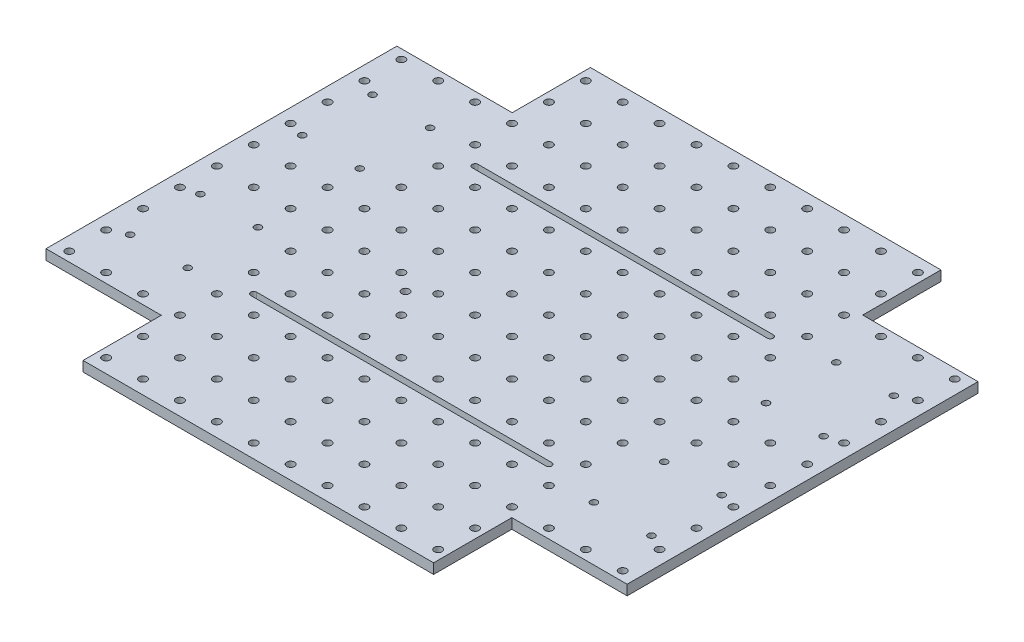
SolidWorks part; units mm, degrees
ref_plane "Front Plane" through (0, 0, 0) normal (0, 0, 1) x (1, 0, 0)
ref_plane "Top Plane" through (0, 0, 0) normal (0, 1, 0) x (1, 0, 0)
ref_plane "Right Plane" through (0, 0, 0) normal (1, 0, 0) x (0, 0, -1)
sketch "Sketch1" plane through (0, 0, 0) normal (0, 1, 0) x (1, 0, 0)
  line L0 (95, -95.1) -> (157.5, -95.1)
  line L1 (-157.5, 95.1) -> (-95, 95.1)
  line L2 (-157.5, 95.1) -> (-157.5, -95.1)
  line L3 (-157.5, -95.1) -> (-95, -95.1)
  line L4 (157.5, 95.1) -> (157.5, -95.1)
  line L5 (-157.5, 95.1) -> (157.5, -95.1) construction
  line L6 (-157.5, -95.1) -> (157.5, 95.1) construction
  line L7 (95, 137.5) -> (-95, 137.5)
  line L8 (95, 137.5) -> (95, 95.1)
  line L9 (95, -137.5) -> (-95, -137.5)
  line L10 (-95, 137.5) -> (-95, 95.1)
  line L11 (95, 137.5) -> (-95, -137.5) construction
  line L12 (95, -137.5) -> (-95, 137.5) construction
  line L13 (95, -95.1) -> (95, -137.5)
  line L14 (-95, -95.1) -> (-95, -137.5)
  line L15 (95, 95.1) -> (157.5, 95.1)
  point P0 (0, 0)
  point P6 (0, 0)
  dimension "D1" = 315
  dimension "D2" = 42.4
  dimension "D3" = 275
  dimension "D4" = 190
extrude "Boss-Extrude1" add sketch "Sketch1" along normal blind 5.4864
sketch "Sketch2" plane through (0, 5.4864, 0) normal (0, 1, 0) x (1, 0, 0)
  line L0 (0, 0) -> (150, 0) construction
  line L1 (150, 0) -> (150, -130) construction
  line L2 (150, -130) -> (130, -130) construction
  line L3 (150, -110) -> (130, -110) construction
  line L4 (150, -90) -> (130, -90) construction
  line L5 (150, -70) -> (130, -70) construction
  line L6 (150, -50) -> (130, -50) construction
  line L7 (150, -30) -> (130, -30) construction
  line L8 (150, -10) -> (130, -10) construction
  line L9 (150, 10) -> (130, 10) construction
  line L10 (150, 30) -> (130, 30) construction
  line L11 (150, 50) -> (130, 50) construction
  line L12 (150, 70) -> (130, 70) construction
  line L13 (150, 90) -> (130, 90) construction
  line L14 (150, 110) -> (130, 110) construction
  line L15 (150, -130) -> (150, -110) construction
  line L16 (150, 130) -> (130, 130) construction
  line L17 (150, 150) -> (130, 150) construction
  circle A0 centre (150, -130) radius 2.1 construction
  circle A1 centre (130, -130) radius 2.1 construction
  circle A2 centre (110, -130) radius 2.1 construction
  circle A3 centre (90, -130) radius 2.1
  circle A4 centre (70, -130) radius 2.1
  circle A5 centre (50, -130) radius 2.1
  circle A6 centre (30, -130) radius 2.1
  circle A7 centre (10, -130) radius 2.1
  circle A8 centre (-10, -130) radius 2.1
  circle A9 centre (-30, -130) radius 2.1
  circle A10 centre (-50, -130) radius 2.1
  circle A11 centre (-70, -130) radius 2.1
  circle A12 centre (-90, -130) radius 2.1
  circle A13 centre (-110, -130) radius 2.1
  circle A14 centre (-130, -130) radius 2.1 construction
  circle A15 centre (-150, -130) radius 2.1 construction
  circle A17 centre (150, -110) radius 2.1 construction
  circle A18 centre (130, -110) radius 2.1 construction
  circle A19 centre (110, -110) radius 2.1 construction
  circle A20 centre (90, -110) radius 2.1
  circle A21 centre (70, -110) radius 2.1
  circle A22 centre (50, -110) radius 2.1
  circle A23 centre (30, -110) radius 2.1
  circle A24 centre (10, -110) radius 2.1
  circle A25 centre (-10, -110) radius 2.1
  circle A26 centre (-30, -110) radius 2.1
  circle A27 centre (-50, -110) radius 2.1
  circle A28 centre (-70, -110) radius 2.1
  circle A29 centre (-90, -110) radius 2.1
  circle A30 centre (-110, -110) radius 2.1
  circle A31 centre (-130, -110) radius 2.1 construction
  circle A32 centre (-150, -110) radius 2.1 construction
  circle A34 centre (150, -90) radius 2.1
  circle A35 centre (130, -90) radius 2.1
  circle A36 centre (110, -90) radius 2.1
  circle A37 centre (90, -90) radius 2.1
  circle A38 centre (70, -90) radius 2.1
  circle A39 centre (50, -90) radius 2.1
  circle A40 centre (30, -90) radius 2.1
  circle A41 centre (10, -90) radius 2.1
  circle A42 centre (-10, -90) radius 2.1
  circle A43 centre (-30, -90) radius 2.1
  circle A44 centre (-50, -90) radius 2.1
  circle A45 centre (-70, -90) radius 2.1
  circle A46 centre (-90, -90) radius 2.1
  circle A47 centre (-110, -90) radius 2.1
  circle A48 centre (-130, -90) radius 2.1
  circle A49 centre (-150, -90) radius 2.1
  circle A51 centre (150, -70) radius 2.1
  circle A52 centre (130, -70) radius 2.1 construction
  circle A53 centre (110, -70) radius 2.1 construction
  circle A54 centre (90, -70) radius 2.1
  circle A55 centre (70, -70) radius 2.1
  circle A56 centre (50, -70) radius 2.1
  circle A57 centre (30, -70) radius 2.1
  circle A58 centre (10, -70) radius 2.1
  circle A59 centre (-10, -70) radius 2.1
  circle A60 centre (-30, -70) radius 2.1
  circle A61 centre (-50, -70) radius 2.1
  circle A62 centre (-70, -70) radius 2.1
  circle A63 centre (-90, -70) radius 2.1
  circle A64 centre (-110, -70) radius 2.1 construction
  circle A65 centre (-130, -70) radius 2.1 construction
  circle A66 centre (-150, -70) radius 2.1
  circle A68 centre (150, -50) radius 2.1
  circle A69 centre (130, -50) radius 2.1 construction
  circle A70 centre (110, -50) radius 2.1 construction
  circle A71 centre (90, -50) radius 2.1
  circle A72 centre (70, -50) radius 2.1
  circle A73 centre (50, -50) radius 2.1
  circle A74 centre (30, -50) radius 2.1
  circle A75 centre (10, -50) radius 2.1
  circle A76 centre (-10, -50) radius 2.1
  circle A77 centre (-30, -50) radius 2.1
  circle A78 centre (-50, -50) radius 2.1
  circle A79 centre (-70, -50) radius 2.1
  circle A80 centre (-90, -50) radius 2.1
  circle A81 centre (-110, -50) radius 2.1 construction
  circle A82 centre (-130, -50) radius 2.1 construction
  circle A83 centre (-150, -50) radius 2.1
  circle A85 centre (150, -30) radius 2.1
  circle A86 centre (130, -30) radius 2.1 construction
  circle A87 centre (110, -30) radius 2.1 construction
  circle A88 centre (90, -30) radius 2.1
  circle A89 centre (70, -30) radius 2.1
  circle A90 centre (50, -30) radius 2.1
  circle A91 centre (30, -30) radius 2.1
  circle A92 centre (10, -30) radius 2.1
  circle A93 centre (-10, -30) radius 2.1
  circle A94 centre (-30, -30) radius 2.1
  circle A95 centre (-50, -30) radius 2.1
  circle A96 centre (-70, -30) radius 2.1
  circle A97 centre (-90, -30) radius 2.1
  circle A98 centre (-110, -30) radius 2.1 construction
  circle A99 centre (-130, -30) radius 2.1 construction
  circle A100 centre (-150, -30) radius 2.1
  circle A102 centre (150, -10) radius 2.1
  circle A103 centre (130, -10) radius 2.1
  circle A104 centre (110, -10) radius 2.1
  circle A105 centre (90, -10) radius 2.1
  circle A106 centre (70, -10) radius 2.1
  circle A107 centre (50, -10) radius 2.1
  circle A108 centre (30, -10) radius 2.1
  circle A109 centre (10, -10) radius 2.1
  circle A110 centre (-10, -10) radius 2.1
  circle A111 centre (-30, -10) radius 2.1
  circle A112 centre (-50, -10) radius 2.1
  circle A113 centre (-70, -10) radius 2.1
  circle A114 centre (-90, -10) radius 2.1
  circle A115 centre (-110, -10) radius 2.1
  circle A116 centre (-130, -10) radius 2.1
  circle A117 centre (-150, -10) radius 2.1
  circle A119 centre (150, 10) radius 2.1
  circle A120 centre (130, 10) radius 2.1
  circle A121 centre (110, 10) radius 2.1
  circle A122 centre (90, 10) radius 2.1
  circle A123 centre (70, 10) radius 2.1
  circle A124 centre (50, 10) radius 2.1
  circle A125 centre (30, 10) radius 2.1
  circle A126 centre (10, 10) radius 2.1
  circle A127 centre (-10, 10) radius 2.1
  circle A128 centre (-30, 10) radius 2.1
  circle A129 centre (-50, 10) radius 2.1
  circle A130 centre (-70, 10) radius 2.1
  circle A131 centre (-90, 10) radius 2.1
  circle A132 centre (-110, 10) radius 2.1
  circle A133 centre (-130, 10) radius 2.1
  circle A134 centre (-150, 10) radius 2.1
  circle A136 centre (150, 30) radius 2.1
  circle A137 centre (130, 30) radius 2.1 construction
  circle A138 centre (110, 30) radius 2.1 construction
  circle A139 centre (90, 30) radius 2.1
  circle A140 centre (70, 30) radius 2.1
  circle A141 centre (50, 30) radius 2.1
  circle A142 centre (30, 30) radius 2.1
  circle A143 centre (10, 30) radius 2.1
  circle A144 centre (-10, 30) radius 2.1
  circle A145 centre (-30, 30) radius 2.1
  circle A146 centre (-50, 30) radius 2.1
  circle A147 centre (-70, 30) radius 2.1
  circle A148 centre (-90, 30) radius 2.1
  circle A149 centre (-110, 30) radius 2.1 construction
  circle A150 centre (-130, 30) radius 2.1 construction
  circle A151 centre (-150, 30) radius 2.1
  circle A153 centre (150, 50) radius 2.1
  circle A154 centre (130, 50) radius 2.1 construction
  circle A155 centre (110, 50) radius 2.1 construction
  circle A156 centre (90, 50) radius 2.1
  circle A157 centre (70, 50) radius 2.1
  circle A158 centre (50, 50) radius 2.1
  circle A159 centre (30, 50) radius 2.1
  circle A160 centre (10, 50) radius 2.1
  circle A161 centre (-10, 50) radius 2.1
  circle A162 centre (-30, 50) radius 2.1
  circle A163 centre (-50, 50) radius 2.1
  circle A164 centre (-70, 50) radius 2.1
  circle A165 centre (-90, 50) radius 2.1
  circle A166 centre (-110, 50) radius 2.1 construction
  circle A167 centre (-130, 50) radius 2.1 construction
  circle A168 centre (-150, 50) radius 2.1
  circle A170 centre (150, 70) radius 2.1
  circle A171 centre (130, 70) radius 2.1 construction
  circle A172 centre (110, 70) radius 2.1 construction
  circle A173 centre (90, 70) radius 2.1
  circle A174 centre (70, 70) radius 2.1
  circle A175 centre (50, 70) radius 2.1
  circle A176 centre (30, 70) radius 2.1
  circle A177 centre (10, 70) radius 2.1
  circle A178 centre (-10, 70) radius 2.1
  circle A179 centre (-30, 70) radius 2.1
  circle A180 centre (-50, 70) radius 2.1
  circle A181 centre (-70, 70) radius 2.1
  circle A182 centre (-90, 70) radius 2.1
  circle A183 centre (-110, 70) radius 2.1 construction
  circle A184 centre (-130, 70) radius 2.1 construction
  circle A185 centre (-150, 70) radius 2.1
  circle A187 centre (150, 90) radius 2.1
  circle A188 centre (130, 90) radius 2.1
  circle A189 centre (110, 90) radius 2.1
  circle A190 centre (90, 90) radius 2.1
  circle A191 centre (70, 90) radius 2.1
  circle A192 centre (50, 90) radius 2.1
  circle A193 centre (30, 90) radius 2.1
  circle A194 centre (10, 90) radius 2.1
  circle A195 centre (-10, 90) radius 2.1
  circle A196 centre (-30, 90) radius 2.1
  circle A197 centre (-50, 90) radius 2.1
  circle A198 centre (-70, 90) radius 2.1
  circle A199 centre (-90, 90) radius 2.1
  circle A200 centre (-110, 90) radius 2.1
  circle A201 centre (-130, 90) radius 2.1
  circle A202 centre (-150, 90) radius 2.1
  circle A204 centre (150, 110) radius 2.1
  circle A205 centre (130, 110) radius 2.1
  circle A206 centre (110, 110) radius 2.1
  circle A207 centre (90, 110) radius 2.1
  circle A208 centre (70, 110) radius 2.1
  circle A209 centre (50, 110) radius 2.1
  circle A210 centre (30, 110) radius 2.1
  circle A211 centre (10, 110) radius 2.1
  circle A212 centre (-10, 110) radius 2.1
  circle A213 centre (-30, 110) radius 2.1
  circle A214 centre (-50, 110) radius 2.1
  circle A215 centre (-70, 110) radius 2.1
  circle A216 centre (-90, 110) radius 2.1
  circle A217 centre (-110, 110) radius 2.1
  circle A218 centre (-130, 110) radius 2.1
  circle A219 centre (-150, 110) radius 2.1
  circle A221 centre (150, 130) radius 2.1 construction
  circle A222 centre (130, 130) radius 2.1 construction
  circle A223 centre (110, 130) radius 2.1
  circle A224 centre (90, 130) radius 2.1
  circle A225 centre (70, 130) radius 2.1
  circle A226 centre (50, 130) radius 2.1
  circle A227 centre (30, 130) radius 2.1
  circle A228 centre (10, 130) radius 2.1
  circle A229 centre (-10, 130) radius 2.1
  circle A230 centre (-30, 130) radius 2.1
  circle A231 centre (-50, 130) radius 2.1
  circle A232 centre (-70, 130) radius 2.1
  circle A233 centre (-90, 130) radius 2.1
  circle A234 centre (-110, 130) radius 2.1
  circle A235 centre (-130, 130) radius 2.1 construction
  circle A236 centre (-150, 130) radius 2.1 construction
  circle A238 centre (150, 150) radius 2.1 construction
  circle A239 centre (130, 150) radius 2.1 construction
  circle A240 centre (110, 150) radius 2.1 construction
  circle A241 centre (90, 150) radius 2.1
  circle A242 centre (70, 150) radius 2.1
  circle A243 centre (50, 150) radius 2.1
  circle A244 centre (30, 150) radius 2.1
  circle A245 centre (10, 150) radius 2.1
  circle A246 centre (-10, 150) radius 2.1
  circle A247 centre (-30, 150) radius 2.1
  circle A248 centre (-50, 150) radius 2.1
  circle A249 centre (-70, 150) radius 2.1
  circle A250 centre (-90, 150) radius 2.1
  circle A251 centre (-110, 150) radius 2.1
  circle A252 centre (-130, 150) radius 2.1 construction
  circle A253 centre (-150, 150) radius 2.1 construction
  dimension "D3" = 4.2
  dimension "D1" = 150
  dimension "D2" = 130
  dimension "D5" = 20
  dimension "D7" = 20
  dimension "D4" = 16
  dimension "D6" = 15
extrude "Cut-Extrude1" cut sketch "Sketch2" against normal through all
hole_wizard "Ø3.0mm Clearance Dowel Hole1" positions "Sketch3" profile "Sketch4" hole size "Ø3.0" standard "ANSI Metric" end condition through all
sketch "Sketch3" plane through (-115.8567, 5.4864, -238.7408) normal (0, 1, 0) x (1, 0, 0)
  point P0 (-25.4433, -173.0408)
  point P3 (5.7567, -173.0408)
  point P6 (-25.4433, -211.1408)
  point P9 (5.7567, -211.1408)
  point P12 (225.9567, -173.0408)
  point P15 (257.1567, -173.0408)
  point P18 (225.9567, -211.1408)
  point P21 (257.1567, -211.1408)
  point P24 (225.9567, -304.4408)
  point P27 (225.9567, -266.3408)
  point P30 (257.1567, -266.3408)
  point P33 (257.1567, -304.4408)
  point P36 (-25.4433, -266.3408)
  point P39 (-25.4433, -304.4408)
  point P42 (5.7567, -304.4408)
  point P45 (5.7567, -266.3408)
sketch "Sketch4" plane through (-141.3, 5.4864, -65.7) normal (1, 0, 0) x (0, 0, 1)
  line L0 (0, 0) -> (0, 5.4864)
  line L1 (0, 5.4864) -> (1.85, 5.4864)
  line L2 (1.85, 5.4864) -> (1.85, 0)
  line L3 (1.85, 0) -> (0, 0)
  line L4 (0, -6.35) -> (0, 107.95) construction
  dimension "Thru Hole Dia." = 3.7
  dimension "Thru Hole Depth" = 5.4864
sketch "Sketch5" plane through (0, 5.4864, 0) normal (0, 1, 0) x (1, 0, 0)
  line L0 (-50, 110) -> (-30, 110) construction
  line L1 (-30, 110) -> (-40, 110) construction
  line L2 (-40, 110) -> (-40, -17.7) construction
  circle A0 centre (-40, -17.7) radius 2.1
  dimension "D2" = 4.2
  dimension "D1" = 127.7
extrude "Cut-Extrude2" cut sketch "Sketch5" against normal through all
sketch "Sketch6" plane through (0, 5.4864, 0) normal (0, 1, 0) x (1, 0, 0)
  line L0 (-80, 60) -> (80, 60) construction
  line L1 (-80, -60) -> (80, -60) construction
  line L2 (-80, -60) -> (-80, 60) construction
  line L3 (-80, 60) -> (80, 60) construction
  line L4 (80, -60) -> (80, 60) construction
  line L5 (-80, -60) -> (80, 60) construction
  line L6 (-80, 60) -> (80, -60) construction
  line L7 (-80, 61.6) -> (80, 61.6)
  line L8 (-80, 58.4) -> (80, 58.4)
  line L9 (-80, -60) -> (80, -60) construction
  line L10 (-80, -58.4) -> (80, -58.4)
  line L11 (-80, -61.6) -> (80, -61.6)
  arc A0 (-80, 61.6) -> (-80, 58.4) centre (-80, 60) ccw
  arc A1 (80, 58.4) -> (80, 61.6) centre (80, 60) ccw
  arc A2 (-80, -58.4) -> (-80, -61.6) centre (-80, -60) ccw
  arc A3 (80, -61.6) -> (80, -58.4) centre (80, -60) ccw
  point P0 (0, 0)
  point P6 (0, 60)
  point P11 (0, -60)
  dimension "D1" = 120
  dimension "D2" = 160
  dimension "D3" = 3.2
extrude "Cut-Extrude3" cut sketch "Sketch6" against normal through all
